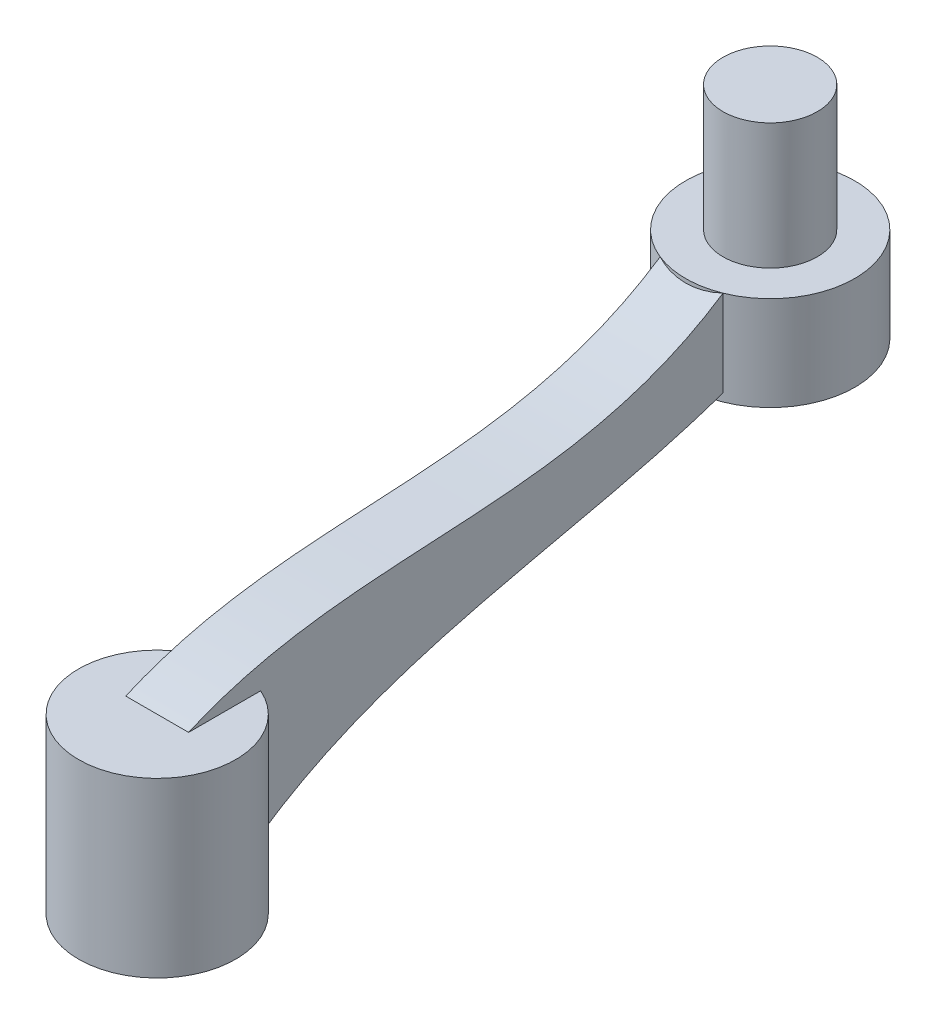
SolidWorks part; units mm, degrees
ref_plane "Front Plane" through (0, 0, 0) normal (0, 0, 1) x (1, 0, 0)
ref_plane "Top Plane" through (0, 0, 0) normal (0, 1, 0) x (1, 0, 0)
ref_plane "Right Plane" through (0, 0, 0) normal (1, 0, 0) x (0, 0, -1)
sketch "Sketch1" plane through (0, 0, 0) normal (0, 1, 0) x (1, 0, 0)
  circle A0 centre (0, 0) radius 7.5005
  circle A1 centre (0, 0) radius 12.5
  dimension "D1" = 15.001
  dimension "D2" = 25
extrude "Boss-Extrude1" add sketch "Sketch1" along normal blind 25
extrude "Boss-Extrude2" add sketch "Sketch1<3>" along normal blind 2.5 from surface contours A1 A0 | A0 region at (0, 0, 0) region at (-12.1464, 0, 0) starting at face at (0, 25, 12.5)
sketch "Sketch1<3>" plane through (0, 0, 0) normal (0, 1, 0) x (1, 0, 0) same geometry as "Sketch1"
sketch "Sketch2" plane through (0, 0, 0) normal (1, 0, 0) x (0, 0, -1)
  line L2 (12.5, 27.5) -> (-12.5, 27.5) construction
  line L4 (110, 45.5) -> (85, 45.5)
  line L5 (0, 27.5) -> (10.0786, 27.5)
  line L6 (10.0786, 27.5) -> (10.0786, 6.753)
  spline S0 degree 3 poles (0, 27.5) (27.3183, 39.4812) (59.3801, 28.4666) (85, 45.5) knots 0 0 0 0 1 1 1 1
  spline S1 degree 3 poles (10.0786, 6.753) (40.2075, 28.5152) (81.4266, 21.3776) (110, 45.5) knots 0 0 0 0 1 1 1 1
  dimension "D1" = 25
  dimension "D2" = 110
  dimension "D3" = 18
extrude "Boss-Extrude5" add sketch "Sketch2" along normal mid plane 10
sketch "Sketch3" plane through (0, 45.5, 0) normal (0, 1, 0) x (1, 0, 0)
  circle A0 centre (0, 97.5) radius 13.4629
extrude "Boss-Extrude6" add sketch "Sketch3" against normal blind 15
sketch "Sketch4" plane through (0, 45.5, 0) normal (0, 1, 0) x (1, 0, 0)
  circle A0 centre (0, 97.5) radius 7.5
  dimension "D1" = 15
extrude "Boss-Extrude7" add sketch "Sketch4" along normal blind 20
